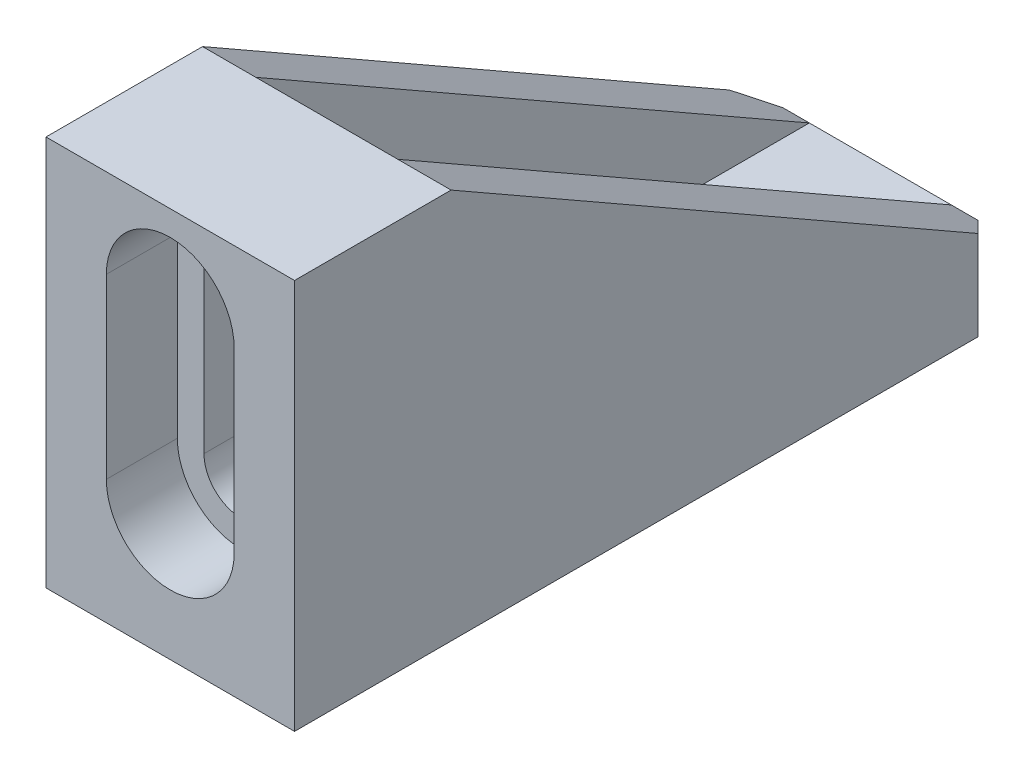
SolidWorks part; units mm, degrees
ref_plane "Alzado" through (0, 0, 0) normal (0, 0, 1) x (1, 0, 0)
ref_plane "Planta" through (0, 0, 0) normal (0, 1, 0) x (1, 0, 0)
ref_plane "Vista lateral" through (0, 0, 0) normal (1, 0, 0) x (0, 0, -1)
sketch "Croquis1" plane through (0, 0, 0) normal (0, 0, 1) x (1, 0, 0)
  line L0 (0, 0) -> (0, 10) construction
  line L1 (-2.1, 0) -> (-2.1, 10)
  line L2 (2.1, 0) -> (2.1, 10)
  line L3 (-7, 7) -> (-7, 15)
  line L4 (-7, 7) -> (7, 7) construction
  line L5 (-7, 7) -> (-7, -7)
  line L6 (-7, -7) -> (7, -7)
  line L7 (7, 7) -> (7, -7)
  line L8 (-7, 7) -> (7, -7) construction
  line L9 (-7, -7) -> (7, 7) construction
  line L10 (-7, 15) -> (7, 15)
  line L11 (7, 15) -> (7, 7)
  arc A1 (-2.1, 0) -> (2.1, 0) centre (0, 0) ccw
  arc A2 (2.1, 10) -> (-2.1, 10) centre (0, 10) ccw
  point P1 (0, 0)
  point P3 (0, 5)
  dimension "D2" = 2.1
  dimension "D1" = 10
  dimension "D3" = 7
  dimension "D4" = 14
extrude "Saliente-Extruir1" add sketch "Croquis1" along normal blind 40
sketch "Croquis2" plane through (0, 0, 40) normal (0, 0, 1) x (1, 0, 0)
  line L0 (0, 0) -> (0, 10) construction
  line L1 (-3.6, 0) -> (-3.6, 10)
  line L2 (3.6, 0) -> (3.6, 10)
  arc A0 (-3.6, 0) -> (3.6, 0) centre (0, 0) ccw
  arc A1 (3.6, 10) -> (-3.6, 10) centre (0, 10) ccw
  point P4 (0, 5)
  dimension "D1" = 3.6
extrude "Cortar-Extruir1" cut sketch "Croquis2" against normal blind 4
sketch "Croquis3" plane through (7, 0, 0) normal (1, 0, 0) x (0, 0, -1)
  line L0 (0, 15) -> (-31.1809, 15)
  line L1 (-40, 15) -> (0, 15) construction
  line L2 (-31.1809, 15) -> (0, -2.8166)
  line L3 (0, -7) -> (0, 15) construction
  line L4 (0, -2.8166) -> (0, 15)
extrude "Cortar-Extruir2" cut sketch "Croquis3" against normal through all
sketch "Croquis4" plane through (0, 15, 0) normal (0, 1, 0) x (1, 0, 0)
  line L0 (-7, 0) -> (7, 0) construction
  line L1 (-4, 0) -> (4, 0)
  line L2 (-4, 0) -> (-4, -31.1809)
  line L3 (-4, -31.1809) -> (4, -31.1809)
  line L4 (4, 0) -> (4, -31.1809)
  line L5 (-4, 0) -> (4, -31.1809) construction
  line L6 (-4, -31.1809) -> (4, 0) construction
  line L7 (-7, -31.1809) -> (7, -31.1809) construction
  line L8 (-7, -31.1809) -> (-7, 0) construction
  line L9 (7, -31.1809) -> (7, 0) construction
  point P4 (0, -15.5904)
  dimension "D1" = 3
  dimension "D2" = 3
extrude "Cortar-Extruir3" cut sketch "Croquis4" against normal up to vertex (17.8166 mm away) up to point (7, -2.8166, 0)
sketch "Croquis5" plane through (0, 0, 31.1809) normal (0, 0, -1) x (-1, 0, 0)
  line L0 (0, 0) -> (0, 50000) construction
  line L2 (-3.45, 13.45) -> (3.45, 13.45)
  line L3 (-3.45, 13.45) -> (-3.45, -3.45)
  line L4 (-3.45, -3.45) -> (3.45, -3.45)
  line L5 (3.45, 13.45) -> (3.45, -3.45)
  line L6 (-3.45, 13.45) -> (3.45, -3.45) construction
  line L7 (-3.45, -3.45) -> (3.45, 13.45) construction
  line L9 (-2.1, 5) -> (49997.9, 5) construction
  line L10 (-2.1, 0) -> (-2.1, 10) construction
  point P3 (0, 5)
  point P8 (3.45, -3.6105)
  point P10 (0, 5)
  point P11 (0, 0)
  point P16 (-2.1, 5)
  dimension "D1" = 6.9
  dimension "D2" = 3.45
extrude "Cortar-Extruir4" cut sketch "Croquis5" against normal offset from surface (1.8191 mm away) 3 up to face at (0, 5, 36)
sketch "Croquis6" plane through (0, -2.8166, 0) normal (0, 1, 0) x (1, 0, 0)
  line L0 (0, 0) -> (0, -50000) construction
  line L1 (-4, -31.1809) -> (4, -31.1809) construction
  circle A0 centre (0, -9.1809) radius 2.5
  circle A1 centre (0, -25.1809) radius 2.5
  dimension "D1" = 5
  dimension "D2" = 5
  dimension "D3" = 16
  dimension "D4" = 6
extrude "Cortar-Extruir5" cut sketch "Croquis6" against normal through all
chamfer "Chaflán1" distance 1.5 angle 45 2 edges at (0, -2.8166, 11.6809) (0, -2.8166, 27.6809)
chamfer "Chaflán2" distance 1.5 angle 45 2 edges at (-7, -4.9083, 0) (7, -4.9083, 0)
